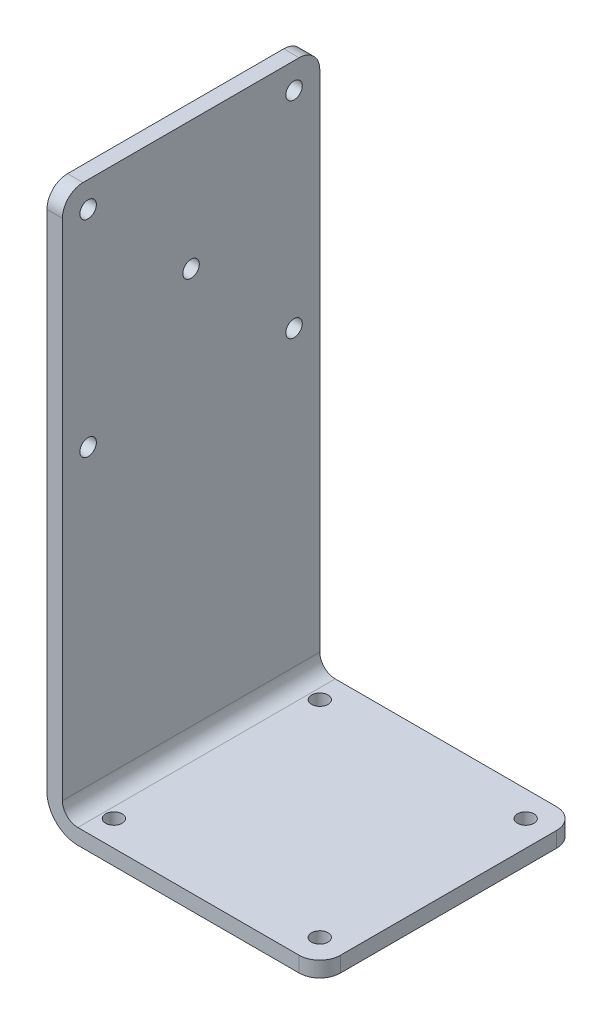
SolidWorks part; units mm, degrees
ref_plane "Front Plane" through (0, 0, 0) normal (0, 0, 1) x (1, 0, 0)
ref_plane "Top Plane" through (0, 0, 0) normal (0, 1, 0) x (1, 0, 0)
ref_plane "Right Plane" through (0, 0, 0) normal (1, 0, 0) x (0, 0, -1)
sketch "Sketch2" plane through (0, 0, 0) normal (0, 1, 0) x (1, 0, 0)
  line L1 (-25, -25) -> (25, -25)
  line L2 (-25, -25) -> (-25, 25)
  line L3 (-25, 25) -> (25, 25)
  line L4 (25, -25) -> (25, 25)
  line L5 (-25, -25) -> (25, 25) construction
  line L6 (-25, 25) -> (25, -25) construction
  point P0 (0, 0)
  dimension "D1" = 50
  dimension "D2" = 50
extrude "Boss-Extrude1" add sketch "Sketch2" along normal blind 3
sketch "Sketch3" plane through (0, 3, 0) normal (0, 1, 0) x (1, 0, 0)
  line L1 (-20, -20) -> (20, -20) construction
  line L2 (-20, -20) -> (-20, 20) construction
  line L3 (-20, 20) -> (20, 20) construction
  line L4 (20, -20) -> (20, 20) construction
  line L5 (-20, -20) -> (20, 20) construction
  line L6 (-20, 20) -> (20, -20) construction
  circle A0 centre (-20, 20) radius 1.6
  circle A1 centre (20, 20) radius 1.6
  circle A2 centre (-20, -20) radius 1.6
  circle A3 centre (20, -20) radius 1.6
  point P1 (0, 0)
  dimension "D2" = 3.2
  dimension "D1" = 40
extrude "Cut-Extrude1" cut sketch "Sketch3" against normal up to surface (3 mm away) up to face at (0, 0, 0)
fillet "Fillet1" radius 4 2 edges at (25, 1.5, -25) (25, 1.5, 25)
sketch "Sketch4" plane through (-25, 0, 0) normal (-1, 0, 0) x (0, 0, 1)
  line L0 (-25, 3) -> (-25, 0) construction
  line L1 (25, 3) -> (25, 0) construction
  line L2 (-25, 0) -> (25, 0) construction
  line L3 (-25, 3) -> (25, 3) construction
  line L4 (-25, 3) -> (-25, 0)
  line L5 (25, 3) -> (25, 0)
  line L6 (-25, 0) -> (25, 0)
  line L7 (-25, 3) -> (25, 3)
extrude "Boss-Extrude2" add sketch "Sketch4" along normal blind 3
sketch "Sketch5" plane through (0, 3, 0) normal (0, 1, 0) x (1, 0, 0)
  line L0 (21, 25) -> (-28, 25) construction
  line L1 (-28, -25) -> (-25, -25)
  line L2 (-28, -25) -> (-28, 25)
  line L3 (-28, 25) -> (-25, 25)
  line L4 (-25, -25) -> (-25, 25)
  dimension "D1" = 3
extrude "Boss-Extrude3" add sketch "Sketch5" along normal blind 55
sketch "Sketch6" plane through (0, 58, 0) normal (0, 1, 0) x (1, 0, 0)
  line L1 (-28, 25) -> (-25, 25)
  line L2 (-28, 25) -> (-28, -25)
  line L3 (-28, -25) -> (-25, -25)
  line L4 (-25, 25) -> (-25, -25)
extrude "Boss-Extrude4" add sketch "Sketch6" along normal blind 50
sketch "Sketch7" plane through (-25, 0, 0) normal (1, 0, 0) x (0, 0, -1)
  line L0 (-20, 103) -> (20, 63) construction
  line L1 (-20, 63) -> (20, 63) construction
  line L2 (-20, 63) -> (-20, 103) construction
  line L3 (-20, 103) -> (20, 103) construction
  line L4 (20, 63) -> (20, 103) construction
  line L5 (-25, 108) -> (25, 108) construction
  line L6 (-25, 108) -> (-25, 3) construction
  line L7 (-25, 58) -> (25, 58) construction
  line L8 (-25, 58) -> (-25, 108) construction
  line L9 (-25, 108) -> (25, 108) construction
  line L10 (25, 58) -> (25, 108) construction
  line L11 (25, 108) -> (25, 3) construction
  line L12 (20, 103) -> (-20, 63) construction
  circle A0 centre (-20, 63) radius 1.6
  circle A1 centre (-20, 103) radius 1.6
  circle A2 centre (20, 103) radius 1.6
  circle A3 centre (20, 63) radius 1.6
  circle A4 centre (0, 83) radius 1.6
  point P6 (0, 108)
  point P7 (0, 103)
  point P16 (-25, 83)
  point P17 (-20, 83)
  dimension "D3" = 3.2
  dimension "D1" = 40
  dimension "D2" = 40
extrude "Cut-Extrude2" cut sketch "Sketch7" against normal up to surface (3 mm away) up to face at (-28, 54, 0)
fillet "Fillet2" radius 4 2 edges at (-26.5, 108, -25) (-26.5, 108, 25)
fillet "Fillet3" radius 3 1 edges at (-25, 3, 0)
fillet "Fillet4" radius 6 1 edges at (-28, 0, 0)
